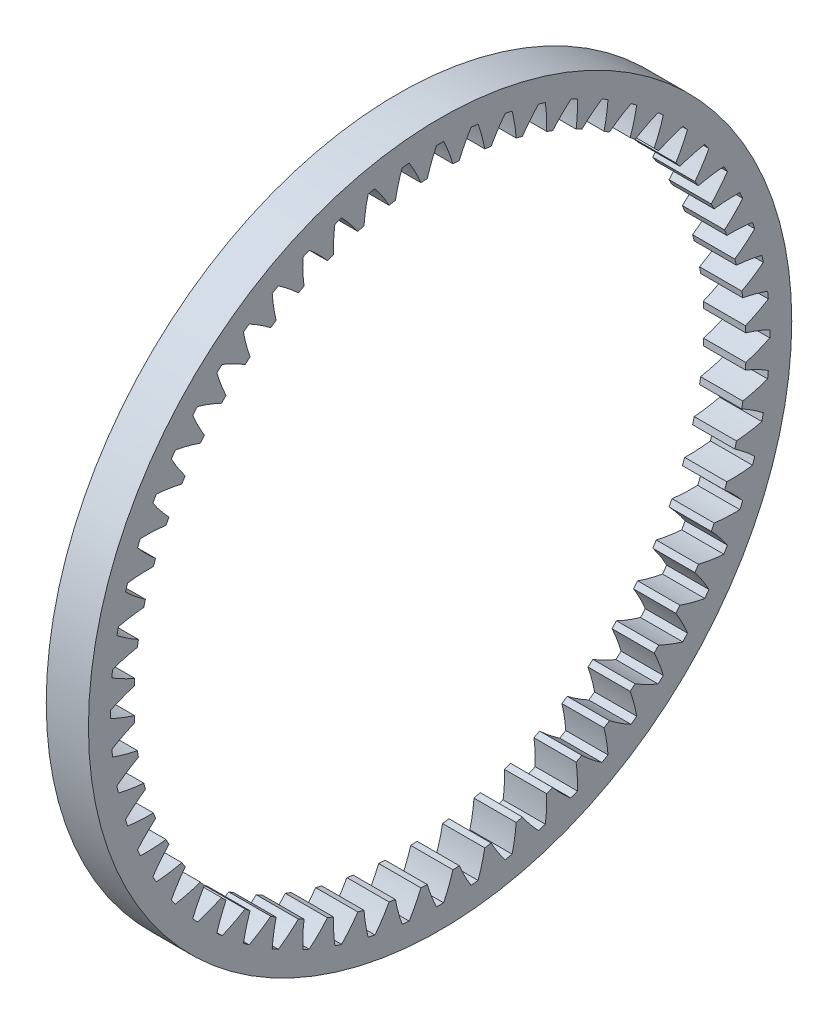
SolidWorks part; units mm, degrees
ref_plane "Plane1" through (0, 0, 0) normal (0, 0, 1) x (1, 0, 0)
ref_plane "Plane2" through (0, 0, 0) normal (0, 1, 0) x (1, 0, 0)
ref_plane "Plane3" through (0, 0, 0) normal (1, 0, 0) x (0, 0, -1)
other "Configuration Table"
sketch "HoldingSke" plane through (0, 0, 0) normal (0, 1, 0) x (1, 0, 0)
  line L0 (0, 0) -> (0.1667, -0.2887)
  line L1 (-15, 0) -> (100, 0) construction
  line L2 (0, 0) -> (-2.1039, 2.3779)
  line L3 (0, 0) -> (-11.863, 4.5341)
  line L4 (0, 0) -> (4.318, 7.479)
  line L5 (0, 0) -> (-23.7986, -8.8762)
  line L6 (0, 0) -> (-10.5278, -7.1032)
  line L7 (-2.1039, 2.3779) -> (3.3635, 27.1825)
  line L8 (-76.2, 5.3779) -> (-54.61, 5.3779)
  line L9 (-71.009, 38.7566) -> (-53.1078, 45.2721)
  line L10 (-76.2, 71.12) -> (104.1128, 71.12)
  line L11 (0, 0) -> (-12, 0)
  line L12 (-76.2, 101.6) -> (-76.093, 101.6)
  line L13 (24.9733, 27.94) -> (52.9518, 28.4284)
  line L14 (24.9733, 27.94) -> (24.9743, 27.94)
  line L15 (24.9733, 27.94) -> (100.4006, 29.5858)
  circle A0 centre (0, 0) radius 100
  circle A1 centre (0, 0) radius 12.7
  circle A2 centre (0, 0) radius 12.7
  dimension "Num_teeth" = 60
  dimension "Pitch_radius" = 180.3128
  dimension "Width" = 12
  dimension "Diameter" = 200
sketch "BasProSke" plane through (0, 0, 0) normal (0, 1, 0) x (1, 0, 0)
  line L0 (-10, 0) -> (60, 0) construction
  line L1 (0, 87) -> (0, 100)
  line L2 (0, 87) -> (12, 87)
  line L3 (12, 87) -> (12, 100)
  line L4 (12, 100) -> (0, 100)
  dimension "Thickness" = 12
  dimension "Diameter" = 200
revolve "Base-Revolve" add sketch "BasProSke" angle 360 about L0
sketch "TooCutSke" plane through (0, 0, 0) normal (1, 0, 0) x (0, 0, -1)
  line L3 (2.6234, 89.9618) -> (2.6234, 53.6633) construction
  line L4 (0, 0) -> (0, 59.563) construction
  line L5 (0, 0) -> (-3.576, 68.2339) construction
  line L6 (-39.5068, 74.1491) -> (33.8074, 77.9913) construction
  circle A0 centre (0, 0) radius 90 construction
  circle A1 centre (0, 0) radius 93.751 construction
  circle A2 centre (0, 0) radius 76.1151 construction
  circle A3 centre (0, 0) radius 86.9746 construction
  arc A4 (3.6494, 86.898) -> (1.0021, 93.7456) centre (-39.5068, 74.1491) ccw
  arc A5 (3.6494, 86.898) -> (-3.6494, 86.898) centre (0, 0) ccw
  arc A6 (1.0021, 93.7456) -> (-1.0021, 93.7456) centre (0, 0) ccw
  arc A7 (-1.0021, 93.7456) -> (-3.6494, 86.898) centre (39.5068, 74.1491) ccw
extrude "ToothCut" cut sketch "TooCutSke" along normal through all
fillet "Breaks" [suppressed] radius 0.3
fillet "RootFillets" [suppressed] radius 0.751
pattern_circular "TeethCuts" count 60 every 6 about axis through (-10, 0, 0) along (1, 0, 0) of "RootFillets", "Breaks", "ToothCut"
equation "' \"Module@HoldingSke\" = 6.35"
equation "' \"Num_teeth@HoldingSke\" = 24"
equation "' \"Ap@HoldingSke\" =  14.5"
equation "' \"Ap@HoldingSke\" = 14.5"
equation "' \"Width@HoldingSke\" = 12"
equation "' \"Diameter@HoldingSke\" = 8 * 25.4"
equation "' \"Show_teeth@HoldingSke\" = 100"
equation "' \"Backlash@HoldingSke\" = 0.009 * 25.4"
equation "' \"Addendum_fac@HoldingSke\" = 1.0"
equation "' \"Dedendum_fac@HoldingSke\" = 1.25"
equation "' \"Dedendum_add@HoldingSke\" = 0.00005 * 25.4"
equation "' \"Clearance_fac@HoldingSke\" = 0.25"
equation "\"Pitch@HoldingSke\" = 1 / \"Module@HoldingSke\" "
equation "\"Overcut_dia@TooCutSke\" = (\"Num_teeth@HoldingSke\" - 2 * \"Addendum_fac@HoldingSke\") / \"Pitch@HoldingSke\" - 0.002 * 25.4"
equation "\"Pitch_dia@TooCutSke\" = \"Num_teeth@HoldingSke\" / \"Pitch@HoldingSke\""
equation "\"Base_dia@TooCutSke\" = \"Num_teeth@HoldingSke\" / \"Pitch@HoldingSke\" * cos((\"Ap@HoldingSke\"  * 3.14159265 / 180)) * 0.90"
equation "\"Root_dia@TooCutSke\" = \"Num_teeth@HoldingSke\"  / \"Pitch@HoldingSke\" + 2 *  \"Dedendum_fac@HoldingSke\"/ \"Pitch@HoldingSke\" + \"Dedendum_add@HoldingSke\" * 2"
equation "\"Half_ang@TooCutSke\" = 180 / \"Num_teeth@HoldingSke\""
equation "\"Half_CT@TooCutSke\" = \"Num_teeth@HoldingSke\" / \"Pitch@HoldingSke\" * sin((3.14159265 / 2 / \"Num_teeth@HoldingSke\")) / 2 + 10 * \"Backlash@HoldingSke\" / 4"
equation "\"Flank_rad@TooCutSke\" = \"Num_teeth@HoldingSke\" / \"Pitch@HoldingSke\" / 4"
equation "\"Radius@RootFillets\"= \"Clearance_fac@HoldingSke\" / \"Pitch@HoldingSke\" + \"Dedendum_add@HoldingSke\""
equation "\"Break_rad@Breaks\" = 0.02 / \"Pitch@HoldingSke\" * 5"
equation "\"Num_teeth@TeethCuts\" = int( \"Show_teeth@HoldingSke\" ) + 1"
equation "\"Num_teeth@TeethCuts\" = ((sgn( \"Num_teeth@TeethCuts\" - \"Num_teeth@HoldingSke\" )-1)*( \"Num_teeth@TeethCuts\" - \"Num_teeth@HoldingSke\" ))/-2+ \"Num_teeth@HoldingSke\""
equation "\"Num_teeth@TeethCuts\" = ((sgn( \"Num_teeth@TeethCuts\" - 2.0)+1)*( \"Num_teeth@TeethCuts\" - 2.0))/2 +2.0"
equation "\"Angle@TeethCuts\" = 360.0 / \"Num_teeth@HoldingSke\""
equation "\"Diameter@BasProSke\" = \"Num_teeth@HoldingSke\"  / \"Pitch@HoldingSke\" + 2 *  \"Dedendum_fac@HoldingSke\"/ \"Pitch@HoldingSke\" + \"Dedendum_add@HoldingSke\" * 2 + 0.002 * 25.4"
equation "\"Diameter@BasProSke\" = ((sgn( \"Diameter@BasProSke\"  - \"Diameter@HoldingSke\" )+1)*( \"Diameter@BasProSke\"  - \"Diameter@HoldingSke\" ))/2 + \"Diameter@HoldingSke\""
equation "\"Inside_diameter@BasProSke\" =  (\"Num_teeth@HoldingSke\" - 2 * \"Addendum_fac@HoldingSke\") / \"Pitch@HoldingSke\" "
equation "\"Thickness@BasProSke\"  = \"Width@HoldingSke\""
